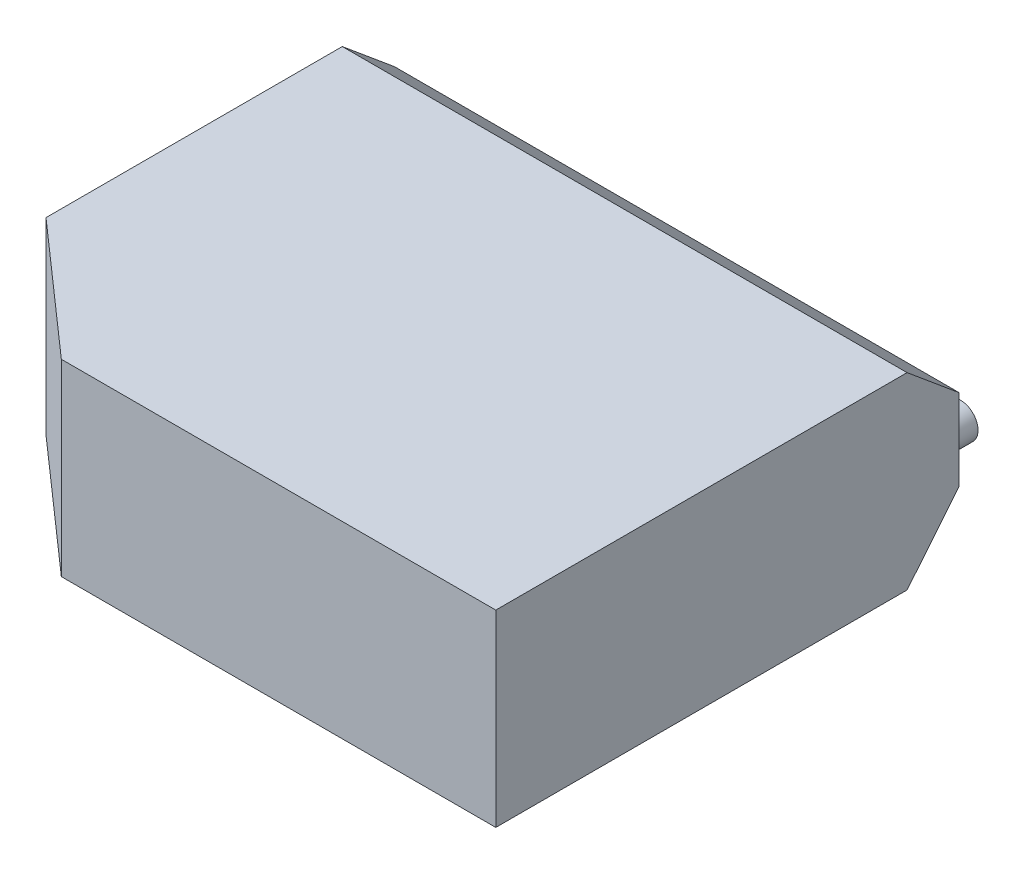
SolidWorks part; units mm, degrees
ref_plane "前视基准面" through (0, 0, 0) normal (0, 0, 1) x (1, 0, 0)
ref_plane "上视基准面" through (0, 0, 0) normal (0, 1, 0) x (1, 0, 0)
ref_plane "右视基准面" through (0, 0, 0) normal (1, 0, 0) x (0, 0, -1)
sketch "草图1" plane through (0, 0, 0) normal (0, 0, 1) x (1, 0, 0)
  line L0 (0, 0) -> (19.5, 0)
  line L1 (19.5, 0) -> (19.5, 6.5)
  line L2 (19.5, 6.5) -> (0, 6.5)
  line L3 (0, 6.5) -> (0, 0)
  dimension "D1" = 19.5
  dimension "D2" = 6.5
extrude "凸台-拉伸1" add sketch "草图1" along normal blind 16
sketch "草图2" plane through (0, 0, 0) normal (0, -1, 0) x (1, 0, 0)
  line L0 (4.5, 16.8254) -> (4.5, 14.2075) construction
  line L1 (-3.0627, 12) -> (2.9958, 12) construction
  line L2 (4.5, 16) -> (-0.0334, 12)
  line L3 (0, 16) -> (19.5, 16) construction
  line L4 (-0.0334, 12) -> (0, 16)
  line L5 (0, 16) -> (4.5, 16)
  dimension "D1" = 15
  dimension "D2" = 12
extrude "切除-拉伸1" cut sketch "草图2" against normal through all
sketch "草图3" plane through (0, 0, 0) normal (0, -1, 0) x (1, 0, 0)
  line L0 (4.5, 6.0148) -> (15, 6.0148) construction
  line L3 (0, 2.121) -> (19.5, 2.121) construction
  line L4 (0, 12.0295) -> (0, 0) construction
  line L5 (19.5, 16) -> (19.5, 0) construction
  text T0 "KBL608" height in points 5
  text T1 "+   AC   -" height in points 5
wrap "包覆1" sketch "草图3" wrap type scribe source sketch "草图3" face at (8.7, 0, 8.8059)
sketch "草图4" plane through (19.5, 0, 0) normal (1, 0, 0) x (0, 0, -1)
  line L0 (-17.505, 2.2) -> (2.6129, 2.2) construction
  line L1 (-16, 0) -> (0, 0) construction
  line L2 (-1.8, -2.3636) -> (-1.8, 8.9027) construction
  line L3 (-0.6817, 3.25) -> (1.4498, 3.25) construction
  line L4 (-1.8, 0) -> (0, 2.2)
  line L6 (0, 0) -> (0, 6.5) construction
  line L7 (0, 5) -> (-1.8, 6.5)
  line L8 (-16, 6.5) -> (0, 6.5) construction
  line L9 (-1.8, 6.5) -> (0, 6.5)
  line L10 (0, 6.5) -> (0, 5)
  line L11 (-1.8, 0) -> (0, 0)
  line L12 (0, 0) -> (0, 2.2)
  dimension "D1" = 2.2
  dimension "D2" = 1.8
extrude "切除-拉伸2" cut sketch "草图4" against normal through all
sketch "草图5" plane through (0, 0, 0) normal (0, 0, -1) x (-1, 0, 0)
  line L0 (-9.75, -1.1551) -> (-9.75, 7.6791) construction
  line L1 (0, 2.2) -> (-19.5, 2.2) construction
  circle A0 centre (-12.35, 2.2) radius 0.6
  circle A1 centre (-17.55, 2.2) radius 0.6
  circle A2 centre (-7.15, 2.2) radius 0.6
  circle A3 centre (-1.95, 2.2) radius 0.6
  dimension "D2" = 1.2
  dimension "D3" = 5.2
  dimension "D4" = 1.2
  dimension "D5" = 5.2
  dimension "D1" = 9.75
extrude "凸台-拉伸2" add sketch "草图5" along normal blind 2 and the other way blind 2
